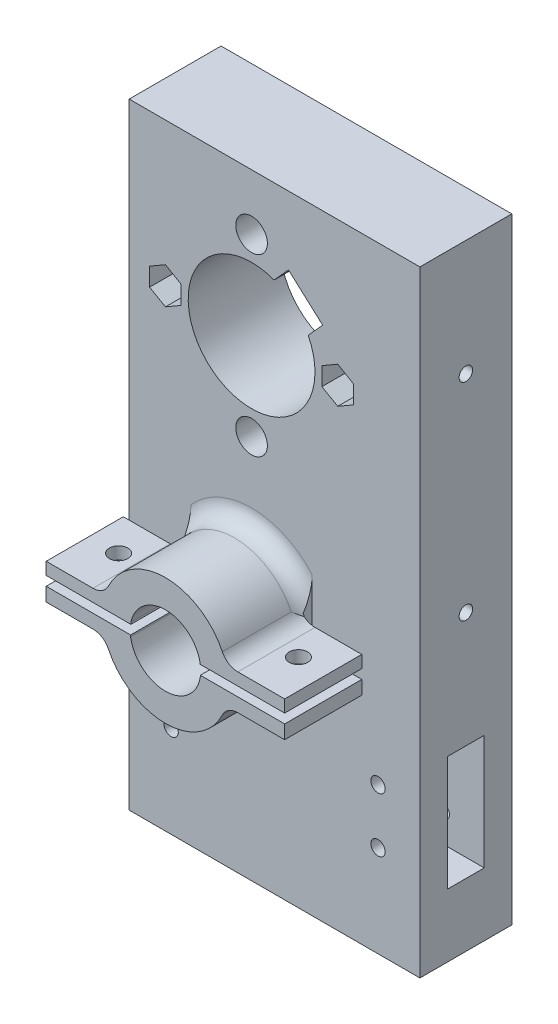
SolidWorks part; units mm, degrees
other "Markup1"
sketch "Sketch8" plane through (21.3115, 25, 0) normal (0.306, 0.1864, -0.9336) x (-0.9512, 0.0181, -0.3081)
ref_plane "Front Plane" through (0, 0, 0) normal (0, 0, 1) x (1, 0, 0)
ref_plane "Top Plane" through (0, 0, 0) normal (0, 1, 0) x (1, 0, 0)
ref_plane "Right Plane" through (0, 0, 0) normal (1, 0, 0) x (0, 0, -1)
sketch "Sketch1" plane through (0, 0, 0) normal (0, 0, 1) x (1, 0, 0)
  line L0 (0, 25) -> (0, -25) construction
  line L1 (21.3115, 25) -> (-21.3115, 25)
  line L2 (21.3115, 25) -> (21.3115, -25)
  line L3 (21.3115, -25) -> (-21.3115, -25)
  line L4 (-21.3115, 25) -> (-21.3115, -25)
  line L5 (21.3115, 25) -> (-21.3115, -25) construction
  line L6 (21.3115, -25) -> (-21.3115, 25) construction
  line L7 (-21.3115, 0) -> (21.3115, 0) construction
  circle A4 centre (0, 15.25) radius 2.75
  circle A5 centre (0, -15.25) radius 2.75
  point P0 (0, 0)
  dimension "D4" = 30.5
  dimension "D2" = 5.5
  dimension "D1" = 5.5
  dimension "D3" = 50
extrude "Boss-Extrude1" add sketch "Sketch1" along normal blind 16
sketch "Sketch2" plane through (0, 0, 0) normal (0, 0, 1) x (1, 0, 0)
  circle A0 centre (0, 0) radius 11.04
  dimension "D1" = 22.08
extrude "Cut-Extrude2" cut sketch "Sketch2" along normal through all
sketch "Sketch3" plane through (0, 0, 0) normal (0, 0, -1) x (-1, 0, 0)
  line L0 (0, 0) -> (-18.0234, 0) construction
  line L1 (0, 0) -> (0, 5.0894) construction
  circle A0 centre (-15, 0) radius 1.75
  circle A1 centre (15, 0) radius 1.75
  dimension "D1" = 15
  dimension "D2" = 3.5
extrude "Cut-Extrude3" cut sketch "Sketch3" against normal blind 10
sketch "Sketch9" plane through (0, 0, 0) normal (0, 0, -1) x (-1, 0, 0)
  line L0 (0, -11.04) -> (0, 11.04) construction
  line L1 (-15, 3.1754) -> (-17.75, 1.5877)
  line L2 (-17.75, 1.5877) -> (-17.75, -1.5877)
  line L3 (-17.75, -1.5877) -> (-15, -3.1754)
  line L4 (-15, -3.1754) -> (-12.25, -1.5877)
  line L5 (-12.25, -1.5877) -> (-12.25, 1.5877)
  line L6 (-12.25, 1.5877) -> (-15, 3.1754)
  line L7 (12.25, 1.5877) -> (15, 3.1754)
  line L8 (12.25, -1.5877) -> (12.25, 1.5877)
  line L9 (15, -3.1754) -> (12.25, -1.5877)
  line L10 (17.75, -1.5877) -> (15, -3.1754)
  line L11 (17.75, 1.5877) -> (17.75, -1.5877)
  line L12 (15, 3.1754) -> (17.75, 1.5877)
  circle A0 centre (-15, 0) radius 2.75 construction
  circle A1 centre (0, 0) radius 11.04 construction
  point P1 (-17.75, 0)
  dimension "D1" = 5.5
extrude "Cut-Extrude6" cut sketch "Sketch9" against normal through all from offset 5 offset against normal yes
sketch "Sketch30" plane through (0, -25, 0) normal (0, -1, 0) x (1, 0, 0)
  line L1 (-21.3115, 16) -> (21.3115, 16)
  line L2 (-21.3115, 16) -> (-21.3115, 0)
  line L3 (-21.3115, 0) -> (21.3115, 0)
  line L4 (21.3115, 16) -> (21.3115, 0)
extrude "Boss-Extrude8" add sketch "Sketch30" along normal blind 20.23
sketch "Sketch10" plane through (0, 0, 0) normal (0, 0, 1) x (1, 0, 0)
  line L0 (21.3115, -45.23) -> (-21.3115, -45.23)
  line L2 (-21.3115, -45.23) -> (-21.3115, -67.23)
  line L3 (-21.3115, -67.23) -> (21.3115, -67.23)
  line L4 (21.3115, -67.23) -> (21.3115, -45.23)
  dimension "D1" = 22
extrude "Boss-Extrude2" add sketch "Sketch10" along normal up to surface (16 mm away) up to face at (15, 0, 16)
sketch "Sketch14" plane through (-21.3115, 0, 0) normal (-1, 0, 0) x (0, 0, 1)
  line L0 (16, -67.23) -> (0, -67.23) construction
  line L1 (4.8, -67.23) -> (11.2, -67.23)
  line L2 (4.8, -67.23) -> (4.8, -51.23)
  line L3 (4.8, -51.23) -> (11.2, -51.23)
  line L4 (11.2, -67.23) -> (11.2, -51.23)
  line L7 (0, -67.23) -> (16, -67.23) construction
  point P6 (8, -67.23)
  point P7 (8, -67.23)
  dimension "D1" = 16
  dimension "D2" = 6.4
extrude "Cut-Extrude7" cut sketch "Sketch14" against normal through all
sketch "Sketch16" plane through (21.3115, 0, 0) normal (1, 0, 0) x (0, 0, -1)
  line L0 (-8, -51.23) -> (-8, 25)
  line L1 (-11.2, -51.23) -> (-4.8, -51.23) construction
  line L2 (-16, 25) -> (0, 25) construction
  line L4 (-16, 25) -> (0, 25)
  line L5 (-16, 25) -> (-16, -51.23)
  line L6 (-16, -51.23) -> (0, -51.23)
  line L7 (0, 25) -> (0, -51.23)
  line M6 (-11.2, -51.23) -> (-4.8, -51.23)
  line M9 (0, -67.23) -> (0, 25)
  line M10 (0, 25) -> (-16, 25)
  line M11 (-16, 25) -> (-16, -67.23)
extrude "Boss-Extrude3" add sketch "Sketch16" along normal blind 8 contours L6 L0 M11 M6 M10 | L6 L0 M6 M9 M10
sketch "Sketch17" plane through (29.3115, 0, 0) normal (1, 0, 0) x (0, 0, -1)
  line L0 (-8, -51.23) -> (-8, 25)
  line L1 (-16, -51.23) -> (0, -51.23) construction
  line L2 (0, 25) -> (-16, 25) construction
  line L3 (-8, -13.115) -> (0, -13.115)
  line L4 (0, -51.23) -> (0, 25) construction
  circle A0 centre (-8, 4.885) radius 1.175
  circle A1 centre (-8, -31.115) radius 1.175
  point P8 (-8, -13.115)
  dimension "D2" = 2.35
  dimension "D1" = 18
extrude "Cut-Extrude9" cut sketch "Sketch17" against normal blind 8 contours L0 A0 | L0 A0 | A1 L0 | A1 L0
sketch "Sketch18" plane through (0, 0, 0) normal (0, 0, -1) x (-1, 0, 0)
  line L0 (-25.3115, -51.23) -> (-25.3115, 25)
  line L1 (-29.3115, -51.23) -> (-21.3115, -51.23) construction
  line L2 (-29.3115, 25) -> (21.3115, 25) construction
  line L3 (-25.3115, -13.115) -> (-29.3115, -13.115)
  line L4 (-26.2115, 6.885) -> (-24.4115, 6.885)
  line L5 (-26.2115, 6.885) -> (-26.2115, 2.885)
  line L6 (-26.2115, 2.885) -> (-24.4115, 2.885)
  line L7 (-24.4115, 6.885) -> (-24.4115, 2.885)
  line L8 (-26.2115, 6.885) -> (-24.4115, 2.885) construction
  line L9 (-26.2115, 2.885) -> (-24.4115, 6.885) construction
  line L10 (-29.3115, -51.23) -> (-29.3115, 25) construction
  line L11 (-26.2115, -29.115) -> (-24.4115, -29.115)
  line L12 (-24.4115, -33.115) -> (-24.4115, -29.115)
  line L13 (-26.2115, -33.115) -> (-24.4115, -33.115)
  line L14 (-26.2115, -33.115) -> (-26.2115, -29.115)
  point P6 (-25.3115, 4.885)
  point P11 (-25.3115, -13.115)
  dimension "D1" = 18
  dimension "D2" = 4
  dimension "D3" = 1.8
extrude "Cut-Extrude10" cut sketch "Sketch18" against normal blind 10.2 contours L7 L4 L0 L6 | L5 L6 L0 L4 | L14 L11 L12 L13
sketch "Sketch20" plane through (0, -51.23, 0) normal (0, -1, 0) x (-1, 0, 0)
  line L1 (-21.3115, -16) -> (-29.3115, -16)
  line L2 (-21.3115, -16) -> (-21.3115, 0)
  line L3 (-21.3115, 0) -> (-29.3115, 0)
  line L4 (-29.3115, -16) -> (-29.3115, 0)
extrude "Boss-Extrude5" add sketch "Sketch20" along normal up to surface (16 mm away) up to face at (0, -67.23, 13.6)
sketch "Sketch21" plane through (0, -67.23, 0) normal (0, -1, 0) x (-1, 0, 0)
  line L0 (-29.3115, -16) -> (-29.3115, 0) construction
  line L1 (-21.3115, -11.2) -> (-29.3115, -11.2)
  line L2 (-21.3115, -11.2) -> (-21.3115, -4.8)
  line L3 (-21.3115, -4.8) -> (-29.3115, -4.8)
  line L4 (-29.3115, -11.2) -> (-29.3115, -4.8)
  line L5 (-21.3115, -4.8) -> (21.3115, -4.8) construction
extrude "Cut-Extrude11" cut sketch "Sketch21" against normal up to surface (16 mm away) up to face at (0, -51.23, 8)
sketch "Sketch24" plane through (0, -67.23, 0) normal (0, -1, 0) x (1, 0, 0)
  line L1 (-21.3115, 4.8) -> (29.3115, 4.8)
  line L2 (-21.3115, 4.8) -> (-21.3115, 0)
  line L3 (-21.3115, 0) -> (29.3115, 0)
  line L4 (29.3115, 4.8) -> (29.3115, 0)
extrude "Boss-Extrude6" add sketch "Sketch24" along normal blind 15
sketch "Sketch25" plane through (0, 0, 4.8) normal (0, 0, 1) x (1, 0, 0)
  line L0 (29.3115, -82.23) -> (-21.3115, -82.23) construction
  line L1 (-21.3115, -82.23) -> (29.3115, -82.23)
  line L2 (-21.3115, -82.23) -> (-21.3115, -67.23)
  line L3 (-21.3115, -67.23) -> (29.3115, -67.23)
  line L4 (29.3115, -82.23) -> (29.3115, -67.23)
extrude "Boss-Extrude7" add sketch "Sketch25" along normal up to surface (11.2 mm away) up to face at (15, 0, 16)
sketch "Sketch26" plane through (0, -82.23, 0) normal (0, -1, 0) x (1, 0, 0)
  line L0 (4, 16) -> (4, 0)
  line L1 (29.3115, 16) -> (-21.3115, 16) construction
  line L2 (-21.3115, 0) -> (29.3115, 0) construction
  line L3 (4, 8) -> (-21.3115, 8)
  line L4 (-21.3115, 16) -> (-21.3115, 0) construction
  circle A0 centre (-14, 8) radius 1
  circle A1 centre (22, 8) radius 1
  dimension "D1" = 2
  dimension "D2" = 18
extrude "Cut-Extrude13" cut sketch "Sketch26" against normal blind 10 contours L3 A0 | L3 A0 | A1
sketch "Sketch27" plane through (0, 0, 0) normal (0, 0, -1) x (-1, 0, 0)
  line L0 (-24.4115, -33.115) -> (-24.4115, -29.115) construction
  line L1 (-24.0015, -77.33) -> (-20.0015, -77.33)
  line L2 (-24.0015, -77.33) -> (-24.0015, -79.13)
  line L3 (-24.0015, -79.13) -> (-20.0015, -79.13)
  line L4 (-20.0015, -77.33) -> (-20.0015, -79.13)
  line L5 (-24.0015, -77.33) -> (-20.0015, -79.13) construction
  line L6 (-24.0015, -79.13) -> (-20.0015, -77.33) construction
  line L8 (-26.2115, -33.115) -> (-24.4115, -33.115) construction
  line L12 (-29.3115, -82.23) -> (-29.3115, 25) construction
  line L13 (21.3115, -82.23) -> (-29.3115, -82.23) construction
  line L14 (-29.3115, -49.5626) -> (21.3115, -49.5626)
  line L15 (21.3115, 25) -> (21.3115, -82.23) construction
  line L16 (-4, -49.5626) -> (-4, -82.23)
  line L17 (16.0015, -79.13) -> (12.0015, -79.13)
  line L18 (12.0015, -77.33) -> (12.0015, -79.13)
  line L19 (16.0015, -77.33) -> (12.0015, -77.33)
  line L20 (16.0015, -77.33) -> (16.0015, -79.13)
  point P0 (-22.0015, -78.23)
  dimension "D1" = 7.31
  dimension "D2" = 3.1
extrude "Cut-Extrude14" cut sketch "Sketch27" against normal blind 10.2 contours L4 L1 L2 L3 | L20 L19 L18 L17
sketch "Sketch32" plane through (0, 0, 16) normal (0, 0, 1) x (1, 0, 0)
  line L24 (10.5609, -36.9231) -> (20.76, -36.9231)
  line L25 (-19.1881, -39.0641) -> (-6.0144, -39.0641)
  line L27 (-18.3513, -40.6918) -> (-6.0688, -40.6918)
  line L29 (-6.0144, -38.7401) -> (-6.0144, -39.0641)
  line L30 (-6.0688, -40.9648) -> (-6.0688, -40.6918)
  line L31 (6.0688, -40.9648) -> (6.0688, -40.6918)
  line L32 (6.0239, -39.0641) -> (6.0144, -38.7401)
  line L33 (6.0239, -39.0641) -> (17.5144, -39.0641)
  line L34 (6.0688, -40.6918) -> (18.3513, -40.6918)
  line L35 (-20.76, -36.9231) -> (-10.5609, -36.9231)
  line L36 (-20.76, -36.9231) -> (-20.76, -39.0641)
  line L37 (-20.76, -43.0769) -> (-10.5609, -43.0769)
  line L38 (20.76, -36.9231) -> (20.76, -39.0641)
  line L39 (10.5609, -43.0769) -> (20.76, -43.0769)
  line L40 (-19.1881, -39.0641) -> (-20.76, -39.0641)
  line L41 (-18.3513, -40.6918) -> (-20.76, -40.6918)
  line L42 (17.5144, -39.0641) -> (20.76, -39.0641)
  line L43 (18.3513, -40.6918) -> (20.76, -40.6918)
  line L44 (-20.76, -40.6918) -> (-20.76, -43.0769)
  line L45 (20.76, -40.6918) -> (20.76, -43.0769)
  line L46 (0, 0) -> (0, -82.23) construction
  line L47 (29.3115, -82.23) -> (-21.3115, -82.23) construction
  arc A0 (-6.0688, -40.9648) -> (6.0688, -40.9648) centre (0, -40) ccw
  arc A1 (-10.5609, -43.0769) -> (10.5609, -43.0769) centre (0, -40) ccw
  arc A2 (10.5609, -36.9231) -> (-10.5609, -36.9231) centre (0, -40) ccw
  arc A3 (6.0144, -38.7401) -> (-6.0144, -38.7401) centre (0, -40) ccw
  dimension "D2" = 6.145
  dimension "D1" = 40
extrude "Boss-Extrude9" add sketch "Sketch32" along normal blind 15
sketch "Sketch35" plane through (0, 0, 16) normal (0, 0, 1) x (1, 0, 0)
  line L0 (0, 0) -> (0, -82.23) construction
  line L1 (29.3115, -82.23) -> (-21.3115, -82.23) construction
  circle A0 centre (0, -40) radius 6.145
  dimension "D1" = 12.29
  dimension "D2" = 40
extrude "Cut-Extrude17" cut sketch "Sketch35" against normal through all
sketch "Sketch46" plane through (0, -82.23, 0) normal (0, -1, 0) x (1, 0, 0)
  line L0 (29.3115, 16) -> (-21.3115, 16) construction
  line L2 (-20.76, 31) -> (-20.76, 16) construction
  line L3 (20.76, 31) -> (20.76, 16) construction
  circle A0 centre (-15.66, 23.5) radius 1.6
  circle A1 centre (15.66, 23.5) radius 1.6
  dimension "D1" = 7.5
  dimension "D3" = 5.1
  dimension "D2" = 5.1
extrude "Cut-Extrude29" cut sketch "Sketch46" against normal through all
sketch "Sketch47" plane through (0, 0, 0) normal (0, 1, 0) x (1, 0, 0)
  line L0 (-10.5609, -31) -> (-10.5609, -16) construction
  line L1 (-20.76, -16) -> (-10.5609, -16)
  line L2 (-20.76, -16) -> (-20.76, -17.5701)
  line L3 (-20.76, -17.5701) -> (-10.5609, -17.5701)
  line L4 (-10.5609, -16) -> (-10.5609, -17.5701)
  line L5 (0, 0) -> (0, -33.2951) construction
  line L6 (20.76, -17.5701) -> (10.5609, -17.5701)
  line L7 (10.5609, -16) -> (10.5609, -17.5701)
  line L8 (20.76, -16) -> (10.5609, -16)
  line L9 (20.76, -16) -> (20.76, -17.5701)
extrude "Cut-Extrude30" cut sketch "Sketch47" against normal through all
fillet "Fillet1" radius 3 2 edges at (0, -29, 16) (0, -51, 16)
fillet "Fillet2" radius 3 4 edges at (-10.5609, -43.0769, 25) (-10.5609, -36.9231, 25) (10.5609, -36.9231, 25) (10.5609, -43.0769, 25)
sketch "Sketch49" plane through (0, 0, 0) normal (0, 0, -1) x (-1, 0, 0)
  line L0 (0, 0) -> (-7.3928, 8.1993)
  line L1 (-10.3635, 5.5207) -> (-4.422, 10.8778)
  line L2 (-8.3546, 3.2927) -> (-12.3725, 7.7488)
  line L3 (-12.3725, 7.7488) -> (-6.431, 13.1059)
  line L4 (-6.431, 13.1059) -> (-2.4131, 8.6498)
  line L5 (-8.3546, 3.2927) -> (-2.4131, 8.6498)
  circle A0 centre (0, 0) radius 11.04 construction
  circle M21 centre (0, 0) radius 11.04
  dimension "D1" = 8
  dimension "D2" = 3
extrude "Cut-Extrude31" cut sketch "Sketch49" against normal through all contours L4 L3 L2 L1 | L2 L1 M21 | L4 L1 M21
sketch "Sketch50" plane through (-21.3115, 0, 0) normal (-1, 0, 0) x (0, 0, 1)
  line L0 (4.8, -67.23) -> (4.8, -71.23)
  line L1 (4.8, -71.23) -> (11.2, -71.23)
  line L2 (11.2, -71.23) -> (11.2, -67.23)
  line L4 (4.8, -67.23) -> (11.2, -67.23)
  dimension "D1" = 4
extrude "Cut-Extrude33" cut sketch "Sketch50" against normal through all
sketch "Sketch51" plane through (0, 0, 0) normal (0, 0, -1) x (-1, 0, 0)
  line L0 (-29.3115, -71.23) -> (21.3115, -71.23)
  line L1 (-29.3115, -82.23) -> (-29.3115, 25) construction
  line L2 (21.3115, 25) -> (21.3115, -82.23) construction
  line L3 (21.3115, -82.23) -> (-29.3115, -82.23) construction
  line L4 (-29.3115, -51.23) -> (-29.3115, -71.23) construction
  line L5 (-29.3115, 25) -> (-29.3115, -82.23) construction
  circle A0 centre (-22.0115, -56.73) radius 1.25
  circle A1 centre (-22.0115, -66.23) radius 1.25
  circle A2 centre (14.0115, -56.73) radius 1.25
  circle A3 centre (14.0115, -66.23) radius 1.25
  point P20 (0, 0)
  dimension "D1" = 2.5
  dimension "D2" = 2.5
  dimension "D3" = 2.5
  dimension "D4" = 2.5
  dimension "D5" = 14.5
  dimension "D6" = 14.5
  dimension "D9" = 7.3
  dimension "D10" = 7.3
  dimension "D11" = 7.3
  dimension "D12" = 9.5
  dimension "D13" = 9.5
  dimension "D7" = 11
  dimension "D8" = 7.3
extrude "Cut-Extrude34" cut sketch "Sketch51" against normal through all contours A3 | A0 | A1 | A2
sketch "Sketch52" plane through (0, 0, 0) normal (0, 0, -1) x (-1, 0, 0)
  line L0 (21.3115, -82.23) -> (-29.3115, -82.23) construction
  line L1 (-13.9925, -55.23) -> (6.0075, -55.23)
  line L2 (-13.9925, -55.23) -> (-13.9925, -69.23)
  line L3 (-13.9925, -69.23) -> (6.0075, -69.23)
  line L4 (6.0075, -55.23) -> (6.0075, -69.23)
  line L5 (-20.8187, -56.356) -> (-13.9925, -55.23)
  line L6 (6.0075, -55.23) -> (12.7615, -56.73)
  circle A2 centre (-22.0115, -56.73) radius 1.25 construction
  circle A3 centre (14.0115, -56.73) radius 1.25 construction
  point P7 (12.7615, -56.73)
  point P13 (0, 0)
  dimension "D1" = 13
  dimension "D2" = 27
  dimension "D3" = 20
extrude "Cut-Extrude35" cut sketch "Sketch52" against normal up to next contours L4 L1 L2 L3
